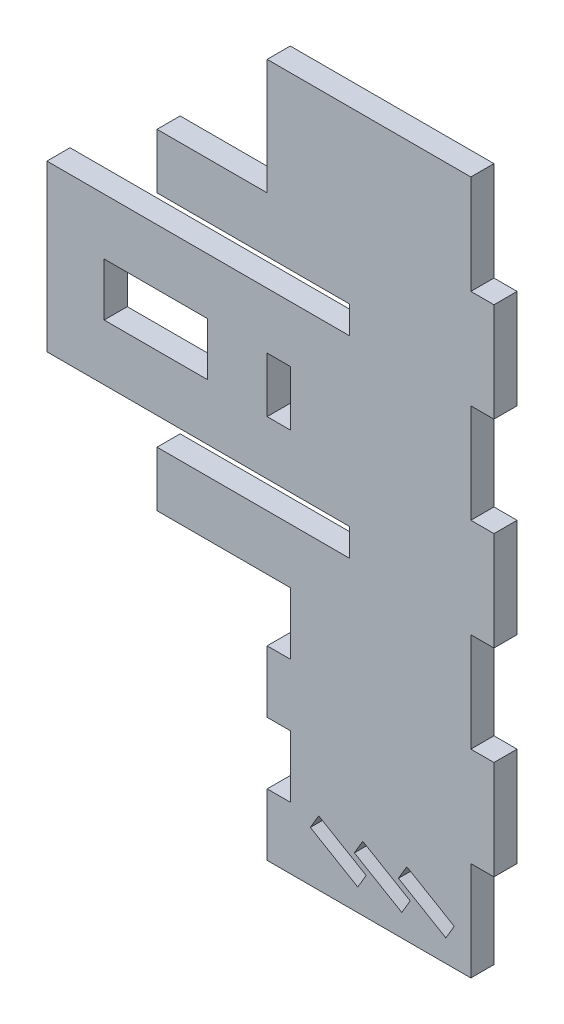
SolidWorks part; units mm, degrees
ref_plane "Front Plane" through (0, 0, 0) normal (0, 0, 1) x (1, 0, 0)
ref_plane "Top Plane" through (0, 0, 0) normal (0, 1, 0) x (1, 0, 0)
ref_plane "Right Plane" through (0, 0, 0) normal (1, 0, 0) x (0, 0, -1)
sketch "Sketch1" plane through (0, 0, 0) normal (0, 0, 1) x (1, 0, 0)
  line L1 (-67.3433, 67.6736) -> (-15.0193, 67.6736)
  line L2 (-67.3433, 67.6736) -> (-67.3433, -92.3464)
  line L3 (-67.3433, -92.3464) -> (-15.0193, -92.3464)
  line L4 (-15.0193, 67.6736) -> (-15.0193, -92.3464)
  dimension "D1" = 160.02
  dimension "D2" = 52.324
extrude "Boss-Extrude1" add sketch "Sketch1" along normal blind 5.334
sketch "Sketch2" plane through (0, 0, 5.334) normal (0, 0, 1) x (1, 0, 0)
  line L0 (-15.0193, -92.3464) -> (-15.0193, 67.6736) construction
  line L1 (-15.0193, 67.6736) -> (-20.3533, 67.6736)
  line L2 (-15.0193, 67.6736) -> (-15.0193, 44.8136)
  line L3 (-15.0193, 44.8136) -> (-20.3533, 44.8136)
  line L4 (-20.3533, 67.6736) -> (-20.3533, 44.8136)
  line L5 (-15.0193, 21.9536) -> (-20.3533, 21.9536)
  line L6 (-15.0193, 21.9536) -> (-15.0193, -0.9064)
  line L7 (-15.0193, -0.9064) -> (-20.3533, -0.9064)
  line L8 (-20.3533, 21.9536) -> (-20.3533, -0.9064)
  line L9 (-20.3533, -69.4864) -> (-20.3533, -46.6264) construction
  line L10 (-15.0193, -23.7664) -> (-20.3533, -23.7664)
  line L11 (-15.0193, -23.7664) -> (-15.0193, -46.6264)
  line L12 (-15.0193, -46.6264) -> (-20.3533, -46.6264)
  line L13 (-20.3533, -23.7664) -> (-20.3533, -46.6264)
  line L14 (-15.0193, -92.3464) -> (-20.3533, -92.3464)
  line L15 (-15.0193, -92.3464) -> (-15.0193, -69.4864)
  line L16 (-15.0193, -69.4864) -> (-20.3533, -69.4864)
  line L17 (-20.3533, -92.3464) -> (-20.3533, -69.4864)
  line L18 (-20.3533, -23.7664) -> (-20.3533, -0.9064) construction
  line L19 (-20.3533, 21.9536) -> (-20.3533, 44.8136) construction
  dimension "D1" = 5.334
extrude "Cut-Extrude1" cut sketch "Sketch2" against normal through all
sketch "Sketch3" plane through (-67.3433, 0, 0) normal (-1, 0, 0) x (0, 0, 1)
  line L0 (0, 67.6736) -> (0, -92.3464) construction
  line L1 (0, 21.9536) -> (5.334, 21.9536)
  line L2 (0, 21.9536) -> (0, -16.1464)
  line L3 (0, -16.1464) -> (5.334, -16.1464)
  line L4 (5.334, 21.9536) -> (5.334, -16.1464)
  line L5 (5.334, 67.6736) -> (5.334, -92.3464) construction
  line L6 (5.334, -92.3464) -> (0, -92.3464) construction
  dimension "D1" = 38.1
  dimension "D2" = 76.2
extrude "Boss-Extrude2" add sketch "Sketch3" along normal blind 50.8
sketch "Sketch4" plane through (0, 0, 5.334) normal (0, 0, 1) x (1, 0, 0)
  line L0 (-67.3433, 21.9536) -> (-67.3433, -16.1464) construction
  line L1 (-104.9353, 8.9996) -> (-81.0593, 8.9996)
  line L2 (-104.9353, 8.9996) -> (-104.9353, -3.1924)
  line L3 (-104.9353, -3.1924) -> (-81.0593, -3.1924)
  line L4 (-81.0593, 8.9996) -> (-81.0593, -3.1924)
  line L5 (-67.3433, 2.9036) -> (-118.1433, 2.9036) construction
  line L6 (-118.1433, -16.1464) -> (-118.1433, 21.9536) construction
  dimension "D1" = 12.192
  dimension "D2" = 6.096
  dimension "D3" = 23.876
  dimension "D4" = 37.084
extrude "Cut-Extrude2" cut sketch "Sketch4" against normal through all
sketch "Sketch5" plane through (0, 0, 5.334) normal (0, 0, 1) x (1, 0, 0)
  line L0 (-118.1433, 2.9036) -> (-30.6389, 2.9036) construction
  line L1 (-67.3433, 21.9536) -> (-48.2933, 21.9536)
  line L2 (-67.3433, 21.9536) -> (-67.3433, 28.3036)
  line L3 (-67.3433, 28.3036) -> (-48.2933, 28.3036)
  line L4 (-48.2933, 21.9536) -> (-48.2933, 28.3036)
  line L5 (-118.1433, -16.1464) -> (-118.1433, 21.9536) construction
  line L6 (-48.2933, -16.1464) -> (-48.2933, -22.4964)
  line L7 (-67.3433, -22.4964) -> (-48.2933, -22.4964)
  line L8 (-67.3433, -16.1464) -> (-67.3433, -22.4964)
  line L9 (-67.3433, -16.1464) -> (-48.2933, -16.1464)
  dimension "D1" = 19.05
  dimension "D2" = 6.35
extrude "Cut-Extrude3" cut sketch "Sketch5" against normal through all
sketch "Sketch6" plane through (-67.3433, 0, 0) normal (-1, 0, 0) x (0, 0, 1)
  line L0 (0, 67.6736) -> (0, 28.3036) construction
  line L1 (5.334, 28.3036) -> (0, 28.3036)
  line L2 (5.334, 28.3036) -> (5.334, 41.0036)
  line L3 (5.334, 41.0036) -> (0, 41.0036)
  line L4 (0, 28.3036) -> (0, 41.0036)
  dimension "D1" = 12.7
extrude "Boss-Extrude3" add sketch "Sketch6" along normal blind 25.4
sketch "Sketch7" plane through (-67.3433, 0, 0) normal (-1, 0, 0) x (0, 0, 1)
  line L0 (5.334, -22.4964) -> (5.334, -92.3464) construction
  line L1 (0, -22.4964) -> (5.334, -22.4964)
  line L2 (0, -22.4964) -> (0, -35.1964)
  line L3 (0, -35.1964) -> (5.334, -35.1964)
  line L4 (5.334, -22.4964) -> (5.334, -35.1964)
  dimension "D1" = 12.7
extrude "Boss-Extrude4" add sketch "Sketch7" along normal blind 25.4
sketch "Sketch8" plane through (0, 0, 5.334) normal (0, 0, 1) x (1, 0, 0)
  line L0 (-67.3433, -35.1964) -> (-67.3433, -92.3464) construction
  line L1 (-67.3433, -35.1964) -> (-62.0093, -35.1964)
  line L2 (-67.3433, -35.1964) -> (-67.3433, -49.4839)
  line L3 (-67.3433, -49.4839) -> (-62.0093, -49.4839)
  line L4 (-62.0093, -35.1964) -> (-62.0093, -49.4839)
  line L5 (-67.3433, -63.7714) -> (-62.0093, -63.7714)
  line L6 (-67.3433, -63.7714) -> (-67.3433, -78.0589)
  line L7 (-67.3433, -78.0589) -> (-62.0093, -78.0589)
  line L8 (-62.0093, -63.7714) -> (-62.0093, -78.0589)
  line L9 (-62.0093, -78.0589) -> (-62.0093, -92.3464) construction
  line L10 (-67.3433, -92.3464) -> (-20.3533, -92.3464) construction
  line L11 (-62.0093, -49.4839) -> (-62.0093, -63.7714) construction
  dimension "D1" = 5.334
extrude "Cut-Extrude4" cut sketch "Sketch8" against normal through all
sketch "Sketch9" plane through (0, 0, 5.334) normal (0, 0, 1) x (1, 0, 0)
  line L0 (-62.0093, -49.4839) -> (-62.0093, -35.1964) construction
  line L1 (-67.3433, 8.9996) -> (-62.0093, 8.9996)
  line L2 (-67.3433, 8.9996) -> (-67.3433, -3.7004)
  line L3 (-67.3433, -3.7004) -> (-62.0093, -3.7004)
  line L4 (-62.0093, 8.9996) -> (-62.0093, -3.7004)
  line L5 (-81.0593, 8.9996) -> (-104.9353, 8.9996) construction
  dimension "D1" = 5.334
  dimension "D2" = 0
  dimension "D3" = 12.7
  dimension "D4" = 0
extrude "Cut-Extrude5" cut sketch "Sketch9" against normal through all
sketch "Sketch10" plane through (0, 0, 5.334) normal (0, 0, 1) x (1, 0, 0)
  line L0 (-37.716, -92.3464) -> (-62.0093, -78.0589) construction
  line L1 (-67.3433, -92.3464) -> (-20.3533, -92.3464) construction
  line L2 (-57.3794, -80.7819) -> (-46.4323, -87.2201)
  line L3 (-57.3794, -80.7819) -> (-55.448, -77.4977)
  line L4 (-46.4323, -87.2201) -> (-44.5009, -83.936)
  line L5 (-55.448, -77.4977) -> (-44.5009, -83.936)
  line L7 (-45.288, -77.4977) -> (-34.3409, -83.936)
  line L8 (-47.2194, -80.7819) -> (-45.288, -77.4977)
  line L9 (-47.2194, -80.7819) -> (-36.2723, -87.2201)
  line L10 (-36.2723, -87.2201) -> (-34.3409, -83.936)
  line L11 (-35.128, -77.4977) -> (-24.1809, -83.936)
  line L12 (-37.0594, -80.7819) -> (-35.128, -77.4977)
  line L13 (-37.0594, -80.7819) -> (-26.1123, -87.2201)
  line L14 (-26.1123, -87.2201) -> (-24.1809, -83.936)
  dimension "D1" = 3.81
  dimension "D2" = 12.7
  dimension "D3" = 3
extrude "Cut-Extrude6" cut sketch "Sketch10" against normal through all
equation "\"MDF\"= .21in"
equation "\"Foamcore\"= .13in"
equation "\"Gmaterial\"= \"MDF\""
equation "\"D2@Sketch1\"=2*\"MDF\"+1.64"
equation "\"D1@Boss-Extrude1\"=\"MDF\""
equation "\"D1@Sketch2\"=\"MDF\""
equation "\"D1@Sketch8\"=\"MDF\""
equation "\"D1@Sketch9\"=\"MDF\""
